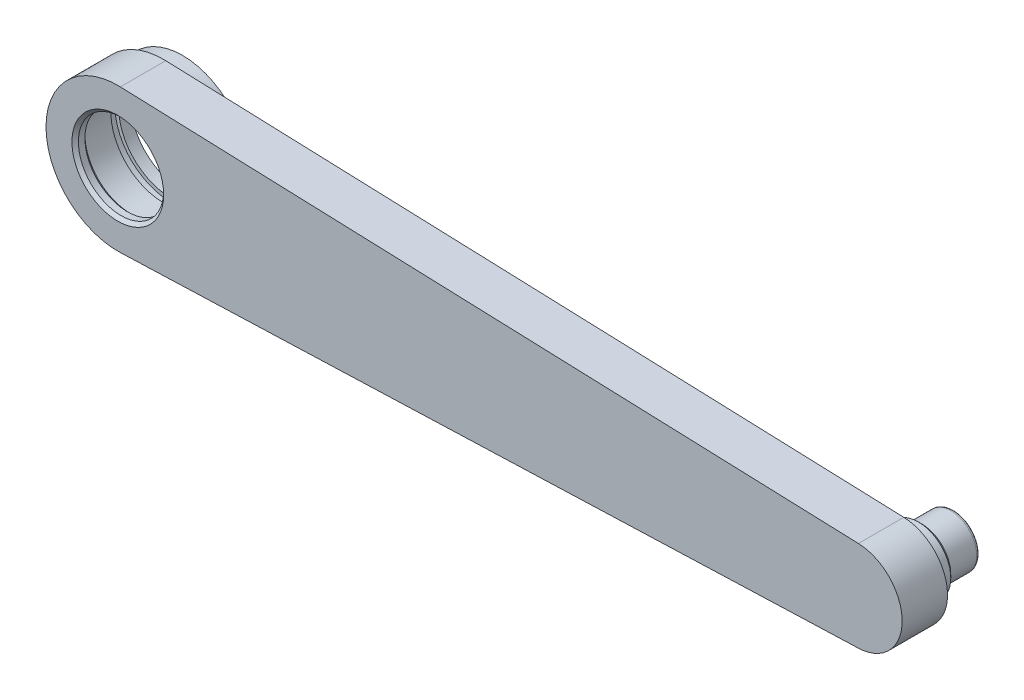
SolidWorks part; units mm, degrees
material "PEI"
ref_plane "前视基准面" through (0, 0, 0) normal (0, 0, 1) x (1, 0, 0)
ref_plane "上视基准面" through (0, 0, 0) normal (0, 1, 0) x (1, 0, 0)
ref_plane "右视基准面" through (0, 0, 0) normal (1, 0, 0) x (0, 0, -1)
other "Configuration Table"
sketch "草图1" plane through (0, 0, 0) normal (0, 0, 1) x (1, 0, 0)
  line L0 (0, 0) -> (114, 0) construction
  line L1 (0.3959, 11.0679) -> (114.2502, 6.9955)
  line L2 (0.3963, -11.0679) -> (114, -7)
  circle A0 centre (114, 0) radius 7
  circle A1 centre (0, 0) radius 8.075
  circle A2 centre (0, 0) radius 11.075
  dimension "D1" = 16.15
  dimension "D3" = 14
  dimension "D2" = 3
  dimension "D4" = 114
extrude "凸台-拉伸1" add sketch "草图1" along normal blind 7 contours A1 A2 | A2 L0 A0 L1 | L0 A2 L2 A0 | A0 region at (7.7447, -7.4723, 0) region at (55.374, 4.6572, 0) region at (55.3681, -4.6561, 0) region at (109.277, 4.895, 0)
sketch "草图2" plane through (0, 0, 7) normal (0, 0, 1) x (1, 0, 0)
  circle A0 centre (0, 0) radius 8.075 construction
  circle A1 centre (0, 0) radius 8.075
  circle A2 centre (0, 0) radius 6.575
  dimension "D1" = 1.5
extrude "凸台-拉伸2" add sketch "草图2" against normal blind 2
sketch "草图3" plane through (0, 0, 0) normal (0, 0, -1) x (-1, 0, 0)
  arc A0 (-114.2502, 6.9955) -> (-114, -7) centre (-114, 0) ccw construction
  arc A1 (-114.2502, 6.9955) -> (-114, -7) centre (-114, 0) ccw
  circle A2 centre (-114, 0) radius 4
  dimension "D1" = 8
extrude "凸台-拉伸3" add sketch "草图3" along normal blind 10 contours A2 region at (114, 0, 0)
sketch "草图4" plane through (0, 0, 0) normal (0, 0, -1) x (-1, 0, 0)
  circle A0 centre (-114, 0) radius 4 construction
  circle A1 centre (-114, 0) radius 4
  circle A2 centre (-114, 0) radius 5
  dimension "D1" = 1
extrude "凸台-拉伸4" add sketch "草图4" along normal blind 3
chamfer "倒角1" distance 0.5 angle 45 4 edges at (6.575, 0, 7) (6.575, 0, 5) (109, 0, -3) (110, 0, -10)
chamfer "倒角2" [suppressed] distance 1 angle 45
sketch "草图5" plane through (0, 0, 0) normal (0, 0, -1) x (-1, 0, 0)
  line L0 (-0.1738, 5.072) -> (-119.0901, 0.9975)
  line L1 (-118.9996, -0.9965) -> (-0.174, -5.072)
  line L2 (-114, -7) -> (-0.3963, -11.0679)
  line L3 (-114, -7) -> (-0.3963, -11.0679)
  line L8 (-0.3959, 11.0679) -> (-114.2502, 6.9955)
  line L9 (-0.3959, 11.0679) -> (-114.2502, 6.9955)
  arc A0 (-119.0901, 0.9975) -> (-118.9996, -0.9965) centre (-119.0945, -0.0017) ccw
  arc A1 (-0.174, -5.072) -> (-0.1738, 5.072) centre (0, 0) ccw
  arc A2 (-0.3963, -11.0679) -> (-0.3959, 11.0679) centre (0, 0) ccw
  arc A3 (-0.3963, -11.0679) -> (-0.3959, 11.0679) centre (0, 0) ccw
  circle A6 centre (-114, 0) radius 5 construction
  arc A12 (-114.2502, 6.9955) -> (-114, -7) centre (-114, 0) ccw
  arc A13 (-114.2502, 6.9955) -> (-114, -7) centre (-114, 0) ccw
  circle A30 centre (0, 0) radius 8.575
  circle A31 centre (-114, 0) radius 5
  circle A32 centre (-114, 0) radius 10
  circle A33 centre (0, 0) radius 13.575
  dimension "D1" = 0
  dimension "D3" = 5
extrude "切除-拉伸1" cut sketch "草图5" against normal up to surface (7 mm away) contours A33 L0 A32 L1 region at (51.0032, 0.0009, 0)
sketch "草图6" plane through (0, 0, 0) normal (0, 0, -1) x (-1, 0, 0)
  line L0 (-104.1142, -1.507) -> (-12.7572, -4.6404) construction
  line L1 (-12.7571, 4.6409) -> (-104.1148, 1.5106) construction
  line L2 (-104.1142, -1.507) -> (-12.7572, -4.6404)
  line L3 (-12.7571, 4.6409) -> (-104.1148, 1.5106)
  line L4 (-12.8598, 7.6391) -> (-104.2175, 4.5089)
  line L5 (-104.217, -4.5053) -> (-12.8601, -7.6387)
  line L6 (-104.2175, 4.5089) -> (-104.1148, 1.5106)
  line L7 (-104.1142, -1.507) -> (-104.217, -4.5053)
  line L8 (-12.8598, 7.6391) -> (-12.7571, 4.6409)
  line L9 (-12.7572, -4.6404) -> (-12.8601, -7.6387)
  dimension "D1" = 3
extrude "切除-拉伸2" cut sketch "草图6" against normal blind 5
sketch "草图7" plane through (0, 0, 0) normal (0, 1, 0) x (1, 0, 0)
  line L0 (117.5, 10) -> (110.5, 10) construction
  line L1 (117.5, 10) -> (110.5, 10)
  line L2 (114, 10) -> (114, 0.7286) construction
  line L4 (110.3, 9) -> (110, 9)
  line L5 (110.3, 9) -> (110.3, 8)
  line L6 (110.3, 8) -> (110, 8)
  line L7 (110, 9) -> (110, 8)
  dimension "D1" = 1
  dimension "D2" = 4
  dimension "D3" = 3.7
  dimension "D4" = 2
revolve "切除-旋转1" [suppressed] cut sketch "草图7" angle 360 about L2
sketch "草图8" plane through (0, 0, -10) normal (0, 0, -1) x (-1, 0, 0)
  circle A0 centre (-114, 0) radius 4 construction
  circle A1 centre (-114, 0) radius 4
extrude "切除-拉伸3" cut sketch "草图8" against normal blind 2
fillet "圆角1" radius 0.5 1 edges at (110, 0, -8)
sketch "草图9" plane through (0, 0, -8) normal (0, 0, -1) x (-1, 0, 0)
  circle A0 centre (-114, 0) radius 2.2
  dimension "D1" = 4.4
extrude "切除-拉伸4" cut sketch "草图9" against normal blind 10
sketch "草图10" plane through (0, 0, 0) normal (0, 0, -1) x (-1, 0, 0)
  circle A0 centre (0, 0) radius 10.075
  circle A1 centre (0, 0) radius 8.075 construction
  circle A2 centre (0, 0) radius 8.075
  dimension "D1" = 2
extrude "凸台-拉伸5" add sketch "草图10" along normal blind 3
sketch "草图11" plane through (0, 0, 0) normal (0, 1, 0) x (1, 0, 0)
  line L0 (8.075, 3) -> (-8.075, 3) construction
  line L1 (5.1574, 1.2) -> (8.65, 1.2)
  line L2 (5.1574, 1.2) -> (5.1574, 0)
  line L3 (5.1574, 0) -> (8.65, 0)
  line L4 (8.65, 1.2) -> (8.65, 0)
  line L5 (0, 0) -> (0, 7.7818) construction
  dimension "D1" = 1.2
  dimension "D2" = 8.65
  dimension "D3" = 3
revolve "切除-旋转2" cut sketch "草图11" angle 360 about L5 region at (6.9037, 0, -0.6)
sketch "草图12" plane through (0, 0, 7) normal (0, 0, 1) x (1, 0, 0)
  line L0 (104.1142, -1.507) -> (12.7572, -4.6404) construction
  line L1 (12.7571, 4.6409) -> (104.1148, 1.5106) construction
  line L2 (104.1142, -1.507) -> (12.7572, -4.6404)
  line L3 (12.7571, 4.6409) -> (104.1148, 1.5106)
  arc A0 (104.1148, 1.5106) -> (104.1142, -1.507) centre (114, 0) ccw construction
  arc A1 (12.7572, -4.6404) -> (12.7571, 4.6409) centre (0, 0) ccw construction
  arc A2 (104.1148, 1.5106) -> (104.1142, -1.507) centre (114, 0) ccw
  arc A3 (12.7572, -4.6404) -> (12.7571, 4.6409) centre (0, 0) ccw
extrude "凸台-拉伸6" add sketch "草图12" against normal up to surface (2 mm away) up to face at (58.4871, -4.5728, 5)
sketch "草图13" plane through (0, 0, 5) normal (0, 0, -1) x (-1, 0, 0)
  line L6 (-104.1142, -1.507) -> (-104.217, -4.5053)
  line L7 (-104.217, -4.5053) -> (-12.8601, -7.6387)
  line L8 (-12.8601, -7.6387) -> (-12.7572, -4.6404)
  line L9 (-12.7571, 4.6409) -> (-12.8598, 7.6391)
  line L10 (-12.8598, 7.6391) -> (-104.2175, 4.5089)
  line L11 (-104.2175, 4.5089) -> (-104.1148, 1.5106)
  line L12 (-104.1142, -1.507) -> (-104.217, -4.5053)
  line L13 (-104.217, -4.5053) -> (-12.8601, -7.6387)
  line L14 (-12.8601, -7.6387) -> (-12.7572, -4.6404)
  line L15 (-12.7571, 4.6409) -> (-12.8598, 7.6391)
  line L16 (-12.8598, 7.6391) -> (-104.2175, 4.5089)
  line L17 (-104.2175, 4.5089) -> (-104.1148, 1.5106)
  arc A2 (-12.7571, 4.6409) -> (-12.7572, -4.6404) centre (0, 0) ccw
  arc A3 (-104.1142, -1.507) -> (-104.1148, 1.5106) centre (-114, 0) ccw
  arc A4 (-12.7571, 4.6409) -> (-12.7572, -4.6404) centre (0, 0) ccw
  arc A5 (-104.1142, -1.507) -> (-104.1148, 1.5106) centre (-114, 0) ccw
  dimension "D1" = 0
extrude "凸台-拉伸7" add sketch "草图13" along normal up to surface (5 mm away) up to face at (58.5751, 0.001, 0)
equation "\"D4@草图1\"= \"连接杆_前_长度\""
equation "\"连接杆_前_长度\"= 114"
